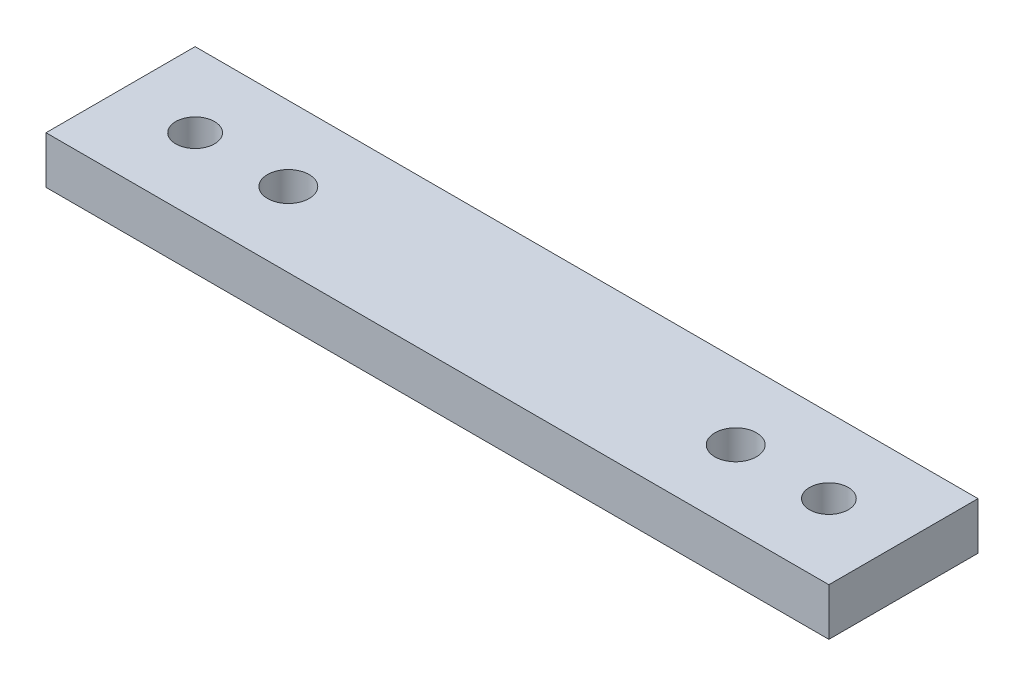
SolidWorks part; units mm, degrees
ref_plane "Front Plane" through (0, 0, 0) normal (0, 0, 1) x (1, 0, 0)
ref_plane "Top Plane" through (0, 0, 0) normal (0, 1, 0) x (1, 0, 0)
ref_plane "Right Plane" through (0, 0, 0) normal (1, 0, 0) x (0, 0, -1)
sketch "Sketch1" plane through (0, 0, 0) normal (0, 1, 0) x (1, 0, 0)
  line L0 (-30, 0) -> (30, 0) construction
  line L1 (-42.5, 0) -> (42.5, 0) construction
  line L2 (-52.5, 10) -> (52.5, 10)
  line L3 (-52.5, 10) -> (-52.5, -10)
  line L4 (-52.5, -10) -> (52.5, -10)
  line L5 (52.5, 10) -> (52.5, -10)
  line L6 (-52.5, 10) -> (52.5, -10) construction
  line L7 (-52.5, -10) -> (52.5, 10) construction
  circle A0 centre (-30, 0) radius 2.794
  circle A1 centre (30, 0) radius 2.794
  circle A2 centre (-42.5, 0) radius 2.6
  circle A3 centre (42.5, 0) radius 2.6
  point P4 (0, 0)
  point P7 (0, 0)
  point P15 (0, 0)
  dimension "D2" = 5.588
  dimension "D3" = 5.588
  dimension "D4" = 5.2
  dimension "D5" = 5.2
  dimension "D1" = 60
  dimension "D6" = 85
  dimension "D7" = 10
  dimension "D8" = 10
extrude "Boss-Extrude1" add sketch "Sketch1" along normal blind 3.175 and the other way blind 3.175
